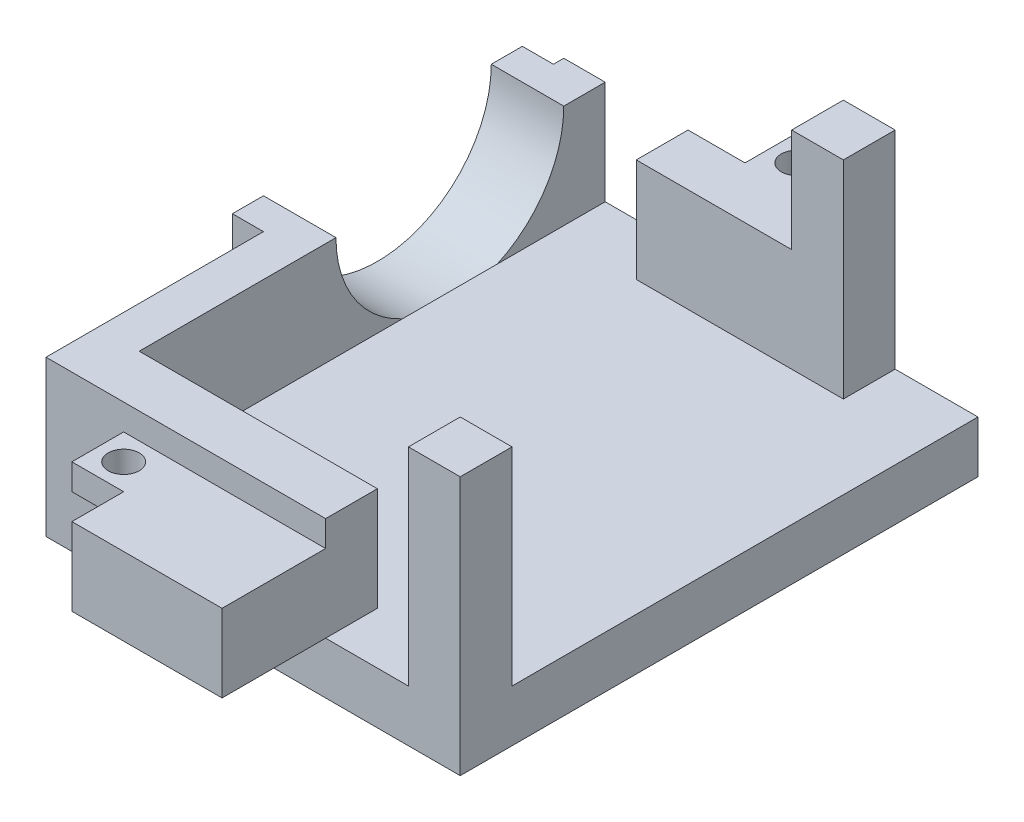
SolidWorks part; units mm, degrees
ref_plane "Front Plane" through (0, 0, 0) normal (0, 0, 1) x (1, 0, 0)
ref_plane "Top Plane" through (0, 0, 0) normal (0, 1, 0) x (1, 0, 0)
ref_plane "Right Plane" through (0, 0, 0) normal (1, 0, 0) x (0, 0, -1)
sketch "Sketch1" plane through (0, 0, 0) normal (0, 1, 0) x (1, 0, 0)
  line L1 (-20, 25) -> (20, 25)
  line L2 (-20, 25) -> (-20, -25)
  line L3 (-20, -25) -> (20, -25)
  line L4 (20, 25) -> (20, -25)
  point P6 (20, 0)
  point P7 (0, 25)
  dimension "D1" = 40
  dimension "D2" = 50
extrude "Boss-Extrude1" add sketch "Sketch1" along normal blind 5
sketch "Sketch3" plane through (0, 5, 0) normal (0, 1, 0) x (1, 0, 0)
  line L0 (20, 25) -> (-20, 25) construction
  line L1 (-8, 25) -> (7, 25)
  line L2 (-8, 25) -> (-8, 20)
  line L3 (-8, 20) -> (7, 20)
  line L4 (7, 25) -> (7, 20)
  line L5 (20, -25) -> (20, 25) construction
  line L6 (-20, -25) -> (20, -25) construction
  line L7 (-20, 25) -> (-16, 25)
  line L10 (-16, 25) -> (-16, -20)
  line L11 (20, -25) -> (15, -25)
  line L12 (20, -25) -> (20, -20)
  line L13 (20, -20) -> (15, -20)
  line L14 (15, -25) -> (15, -20)
  line L15 (7, -25) -> (-20, -25)
  line L16 (7, -25) -> (7, -20)
  line L17 (7, -20) -> (-16, -20)
  line L20 (15, 25) -> (15, 20) construction
  line L21 (15, 20) -> (20, 20) construction
  line L22 (-20, 25) -> (-20, -25)
  line L23 (7, -20) -> (12, -20) construction
  line L24 (12, -20) -> (12, -25) construction
  line L26 (7, 20) -> (12, 20)
  line L27 (7, 20) -> (7, 25)
  line L28 (7, 25) -> (12, 25)
  line L29 (12, 20) -> (12, 25)
  line M17 (-20, 25) -> (-20, -25)
  line M18 (-20, -25) -> (20, -25)
  line M19 (20, -25) -> (20, 25)
  line M20 (20, 25) -> (-20, 25)
  dimension "D1" = 8
  dimension "D2" = 15
  dimension "D3" = 4
  dimension "D4" = 5
  dimension "D5" = 5
  dimension "D7" = 5
  dimension "D8" = 5
  dimension "D9" = 5
extrude "Boss-Extrude5" add sketch "Sketch3" along normal blind 20 contours L14 L13 M18 M19 | L26 L29 L4 M20 region at (9.5, 5, -22.5) region at (17.5, 5, 22.5)
extrude "Boss-Extrude6" add sketch "Sketch3<3>" along normal blind 10 contours L4 L2 L3 M20 | L16 L17 L10 M20 M17 M18 region at (-0.5, 5, -22.5) region at (-16.5682, 5, -2.5)
sketch "Sketch3<3>" plane through (0, 5, 0) normal (0, 1, 0) x (1, 0, 0) same geometry as "Sketch3"
sketch "Sketch8" plane through (-20, 0, 0) normal (-1, 0, 0) x (0, 0, 1)
  line L0 (-25, 15) -> (25, 15) construction
  line L1 (1, 15) -> (-21, 15)
  arc A0 (-21, 15) -> (1, 15) centre (-10, 15) ccw
  dimension "D1" = 22
  dimension "D2" = 4
extrude "Cut-Extrude3" cut sketch "Sketch8" against normal blind 4
sketch "Sketch10" plane through (-20, 0, 0) normal (-1, 0, 0) x (0, 0, 1)
  line L0 (1, 15) -> (4, 15)
  line L1 (1, 15) -> (25, 15) construction
  line L2 (4, 15) -> (4, 0)
  line L3 (-25, 0) -> (25, 0) construction
  line L4 (4, 0) -> (-24, 0)
  line L5 (-24, 0) -> (-24, 15)
  line L6 (-25, 15) -> (-21, 15) construction
  line L7 (-24, 15) -> (-21, 15)
  arc A0 (-21, 15) -> (1, 15) centre (-10, 15) ccw
  dimension "D2" = 11
  dimension "D1" = 3
extrude "Boss-Extrude9" add sketch "Sketch10" along normal blind 3
sketch "Sketch12" plane through (0, 0, -25) normal (0, 0, -1) x (-1, 0, 0)
  line L0 (-7, 15) -> (8, 15) construction
  line L1 (-2.5, 15) -> (2.5, 15)
  line L2 (-2.5, 15) -> (-2.5, 10)
  line L3 (-2.5, 10) -> (2.5, 10)
  line L4 (2.5, 15) -> (2.5, 10)
  point P7 (0, 10)
  dimension "D1" = 5
  dimension "D2" = 5
extrude "Boss-Extrude10" add sketch "Sketch12" along normal blind 5
sketch "Sketch13" plane through (0, 10, 0) normal (0, -1, 0) x (1, 0, 0)
  line L0 (-2.5, -30) -> (-2.5, -25) construction
  line L1 (2.5, -30) -> (-2.5, -30) construction
  circle A0 centre (0, -27.5) radius 1.5
  point P2 (0, 0)
  point P5 (-2.5, -27.5)
  point P8 (0, -30)
  dimension "D1" = 3
extrude "Cut-Extrude4" cut sketch "Sketch13" against normal blind 5
sketch "Sketch16" plane through (0, 0, 25) normal (0, 0, 1) x (1, 0, 0)
  line L0 (7, 5) -> (-7.5, 5)
  line L1 (-7.5, 5) -> (-7.5, 10)
  line L2 (-7.5, 10) -> (-12.5, 10)
  line L3 (-12.5, 10) -> (-12.5, 12.5)
  line L4 (-12.5, 12.5) -> (7, 12.5)
  line L5 (7, 15) -> (7, 5) construction
  line L6 (7, 12.5) -> (7, 5)
  line L7 (-7.5, 10) -> (-7.5, 12.5)
  line M12 (7, 5) -> (7, 15)
  dimension "D1" = 2.5
  dimension "D2" = 5
  dimension "D3" = 7.5
  dimension "D4" = 19.5
extrude "Boss-Extrude13" add sketch "Sketch16" along normal blind 5 contours L2 L7 L4 L3 region at (-10, 11.25, 25)
extrude "Boss-Extrude14" add sketch "Sketch16<3>" along normal blind 10 contours L7 L1 L0 L4 M12 region at (-0.25, 8.75, 25)
sketch "Sketch16<3>" plane through (0, 0, 25) normal (0, 0, 1) x (1, 0, 0) same geometry as "Sketch16"
sketch "Sketch17" plane through (0, 10, 0) normal (0, -1, 0) x (1, 0, 0)
  line L0 (-12.5, 30) -> (-12.5, 25) construction
  line L1 (-7.5, 30) -> (-12.5, 30) construction
  circle A0 centre (-10, 27.5) radius 1.5
  point P4 (-12.5, 27.5)
  point P7 (-10, 30)
  dimension "D1" = 3
extrude "Cut-Extrude6" cut sketch "Sketch17" against normal blind 2.5
